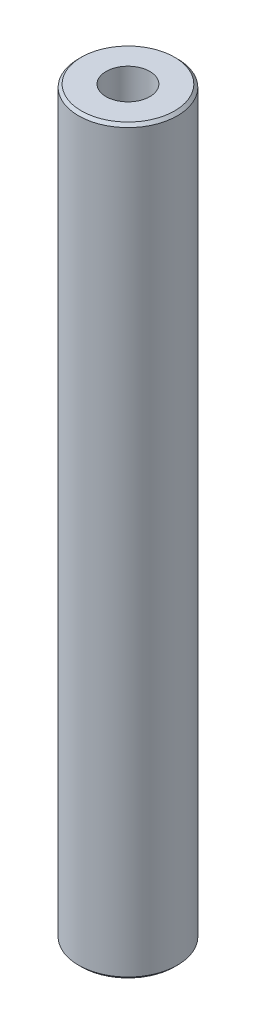
SolidWorks part; units mm, degrees
ref_plane "Front Plane" through (0, 0, 0) normal (0, 0, 1) x (1, 0, 0)
ref_plane "Top Plane" through (0, 0, 0) normal (0, 1, 0) x (1, 0, 0)
ref_plane "Right Plane" through (0, 0, 0) normal (1, 0, 0) x (0, 0, -1)
sketch "Sketch1" plane through (0, 0, 0) normal (0, 1, 0) x (1, 0, 0)
  circle A0 centre (0, 0) radius 40
  dimension "SHAFT_OD" = 80
extrude "Boss-Extrude1" add sketch "Sketch1" along normal blind 600
sketch "Sketch2" plane through (0, 0, 0) normal (0, 1, 0) x (1, 0, 0)
  circle A0 centre (0, 0) radius 17.7134
  dimension "BORE_D" = 35.4268
extrude "Cut-Extrude1" cut sketch "Sketch2" along normal through all
chamfer "Chamfer1" distance 2.2749 angle 45.16 2 edges at (0, 600, 40) (0, 0, 40) first distance on face at (0, 600, 40) first distance on face at (0, 0, 17.7134)
